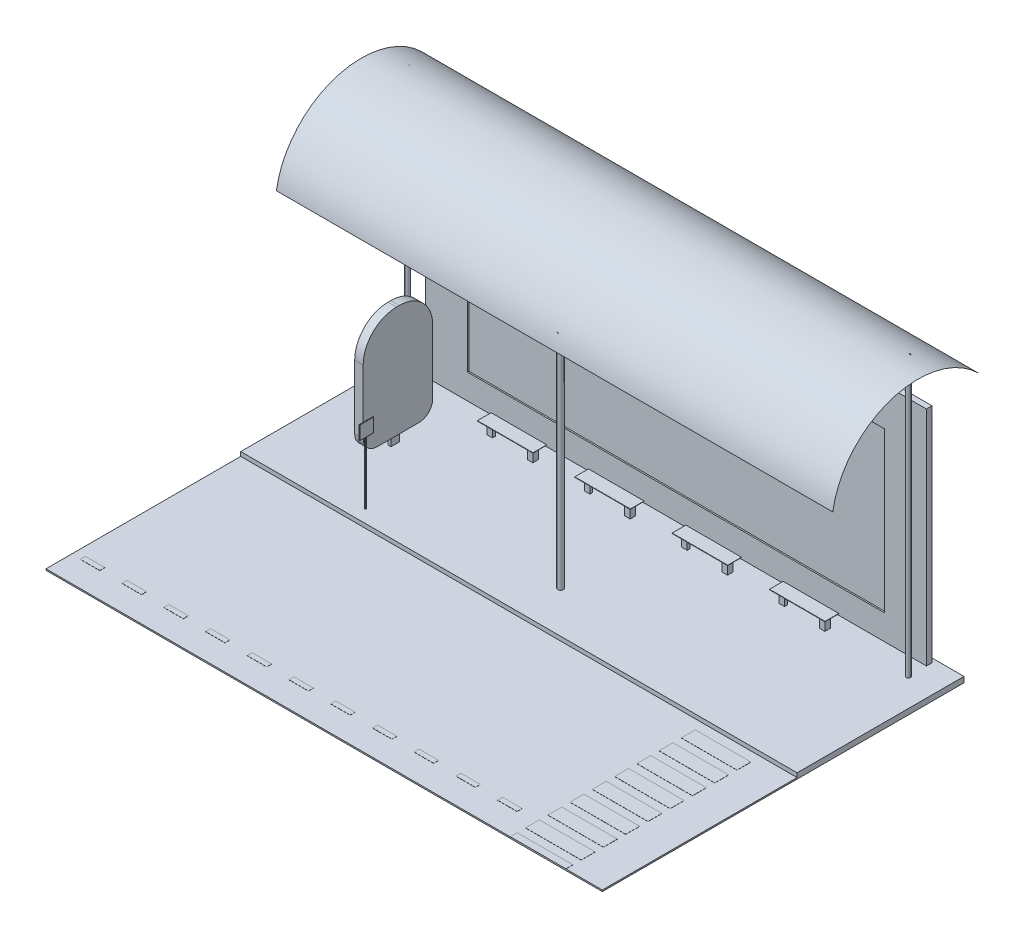
SolidWorks part; units mm, degrees
other "Camera1"
ref_plane "Front Plane" through (0, 0, 0) normal (0, 0, 1) x (1, 0, 0)
ref_plane "Top Plane" through (0, 0, 0) normal (0, 1, 0) x (1, 0, 0)
ref_plane "Right Plane" through (0, 0, 0) normal (1, 0, 0) x (0, 0, -1)
sketch "Sketch1" plane through (0, 0, 0) normal (0, 1, 0) x (1, 0, 0)
  line L1 (-2500, -6500) -> (17500, -6500)
  line L2 (-2500, -6500) -> (-2500, 6500)
  line L3 (-2500, 6500) -> (17500, 6500)
  line L4 (17500, -6500) -> (17500, 6500)
  point P0 (0, 0)
  dimension "D1" = 20000
  dimension "D2" = 13000
extrude "Boss-Extrude1" add sketch "Sketch1" along normal blind 200
sketch "Sketch2" plane through (0, 200, 0) normal (0, 1, 0) x (1, 0, 0)
  line L0 (-2500, 6500) -> (-2500, -6500) construction
  line L1 (17500, -6500) -> (-2500, -6500)
  line L2 (17500, -6500) -> (17500, 500)
  line L3 (17500, 500) -> (-2500, 500)
  line L4 (-2500, -6500) -> (-2500, 500)
  dimension "D1" = 7000
extrude "Calle" cut sketch "Sketch2" against normal blind 150 contours L3 L4 L1 L2
sketch "Sketch5" plane through (0, 50, 0) normal (0, 1, 0) x (1, 0, 0)
  line L0 (17500, -6500) -> (17500, -5500) construction
  line L1 (17500, -6500) -> (17500, 500) construction
  line L3 (17500, -5500) -> (-2500, -5500) construction
  line L4 (-2500, -6500) -> (-2500, 500) construction
  line L9 (24.9879, -5409.4917) -> (-675.0121, -5409.4917)
  line L10 (24.9879, -5590.5083) -> (-675.0121, -5590.5083)
  line L102 (15189.04, -6500) -> (15189.04, 500) construction
  line L107 (16189.04, -5450) -> (14189.04, -5450)
  line L108 (16189.04, -5950) -> (14189.04, -5950)
  line L109 (17500, -6500) -> (-2500, -6500) construction
  line L110 (17500, 500) -> (-2500, 500) construction
  line L111 (16189.04, -6250) -> (15189.04, -6500) construction
  line L112 (15189.04, -6500) -> (14189.04, -6250) construction
  line L113 (16189.04, -6250) -> (14189.04, -6250)
  line L117 (16189.04, -5450) -> (16189.04, -5950)
  line L118 (14189.04, -5450) -> (14189.04, -5950)
  line L119 (16189.04, -5450) -> (14189.04, -5950) construction
  line L120 (16189.04, -5950) -> (14189.04, -5450) construction
  line L121 (16189.04, -4650) -> (14189.04, -4650)
  line L122 (16189.04, -5150) -> (14189.04, -5150)
  line L123 (16189.04, -4650) -> (16189.04, -5150)
  line L124 (14189.04, -4650) -> (14189.04, -5150)
  line L125 (16189.04, -4650) -> (14189.04, -5150) construction
  line L126 (16189.04, -5150) -> (14189.04, -4650) construction
  line L127 (16189.04, -3850) -> (14189.04, -3850)
  line L128 (16189.04, -4350) -> (14189.04, -4350)
  line L129 (16189.04, -3850) -> (16189.04, -4350)
  line L130 (14189.04, -3850) -> (14189.04, -4350)
  line L131 (16189.04, -3850) -> (14189.04, -4350) construction
  line L132 (16189.04, -4350) -> (14189.04, -3850) construction
  line L133 (16189.04, -3050) -> (14189.04, -3050)
  line L134 (16189.04, -3550) -> (14189.04, -3550)
  line L135 (16189.04, -3050) -> (16189.04, -3550)
  line L136 (14189.04, -3050) -> (14189.04, -3550)
  line L137 (16189.04, -3050) -> (14189.04, -3550) construction
  line L138 (16189.04, -3550) -> (14189.04, -3050) construction
  line L139 (16189.04, -2250) -> (14189.04, -2250)
  line L140 (16189.04, -2750) -> (14189.04, -2750)
  line L141 (16189.04, -2250) -> (16189.04, -2750)
  line L142 (14189.04, -2250) -> (14189.04, -2750)
  line L143 (16189.04, -2250) -> (14189.04, -2750) construction
  line L144 (16189.04, -2750) -> (14189.04, -2250) construction
  line L145 (16189.04, -1450) -> (14189.04, -1450)
  line L146 (16189.04, -1950) -> (14189.04, -1950)
  line L147 (16189.04, -1450) -> (16189.04, -1950)
  line L148 (14189.04, -1450) -> (14189.04, -1950)
  line L149 (16189.04, -1450) -> (14189.04, -1950) construction
  line L150 (16189.04, -1950) -> (14189.04, -1450) construction
  line L151 (16189.04, -650) -> (14189.04, -650)
  line L152 (16189.04, -1150) -> (14189.04, -1150)
  line L153 (16189.04, -650) -> (16189.04, -1150)
  line L154 (14189.04, -650) -> (14189.04, -1150)
  line L155 (16189.04, -650) -> (14189.04, -1150) construction
  line L156 (16189.04, -1150) -> (14189.04, -650) construction
  line L157 (16189.04, 150) -> (14189.04, 150)
  line L158 (16189.04, -350) -> (14189.04, -350)
  line L159 (16189.04, 150) -> (16189.04, -350)
  line L160 (14189.04, 150) -> (14189.04, -350)
  line L161 (16189.04, 150) -> (14189.04, -350) construction
  line L162 (16189.04, -350) -> (14189.04, 150) construction
  line L163 (14189.04, -6250) -> (14189.04, -6500)
  line L164 (16189.04, -6250) -> (16189.04, -6500)
  line L165 (14189.04, -6500) -> (16189.04, -6500)
  line L174 (-1475.0121, -5590.5083) -> (-1475.0121, -5409.4917)
  line L175 (-1475.0121, -5409.4917) -> (-2175.0121, -5409.4917)
  line L176 (-1475.0121, -5590.5083) -> (-2175.0121, -5409.4917) construction
  line L177 (-1475.0121, -5590.5083) -> (-2175.0121, -5590.5083)
  line L178 (-2175.0121, -5590.5083) -> (-2175.0121, -5409.4917)
  line L179 (-1475.0121, -5409.4917) -> (-2175.0121, -5590.5083) construction
  line L181 (-675.0121, -5590.5083) -> (-675.0121, -5409.4917)
  line L182 (24.9879, -5590.5083) -> (24.9879, -5409.4917)
  line L183 (1524.9879, -5409.4917) -> (824.9879, -5409.4917)
  line L184 (1524.9879, -5590.5083) -> (824.9879, -5590.5083)
  line L185 (824.9879, -5590.5083) -> (824.9879, -5409.4917)
  line L186 (1524.9879, -5590.5083) -> (1524.9879, -5409.4917)
  line L187 (3024.9879, -5409.4917) -> (2324.9879, -5409.4917)
  line L188 (3024.9879, -5590.5083) -> (2324.9879, -5590.5083)
  line L189 (2324.9879, -5590.5083) -> (2324.9879, -5409.4917)
  line L190 (3024.9879, -5590.5083) -> (3024.9879, -5409.4917)
  line L191 (4524.9879, -5409.4917) -> (3824.9879, -5409.4917)
  line L192 (4524.9879, -5590.5083) -> (3824.9879, -5590.5083)
  line L193 (3824.9879, -5590.5083) -> (3824.9879, -5409.4917)
  line L194 (4524.9879, -5590.5083) -> (4524.9879, -5409.4917)
  line L195 (6024.9879, -5409.4917) -> (5324.9879, -5409.4917)
  line L196 (6024.9879, -5590.5083) -> (5324.9879, -5590.5083)
  line L197 (5324.9879, -5590.5083) -> (5324.9879, -5409.4917)
  line L198 (6024.9879, -5590.5083) -> (6024.9879, -5409.4917)
  line L199 (7524.9879, -5409.4917) -> (6824.9879, -5409.4917)
  line L200 (7524.9879, -5590.5083) -> (6824.9879, -5590.5083)
  line L201 (6824.9879, -5590.5083) -> (6824.9879, -5409.4917)
  line L202 (7524.9879, -5590.5083) -> (7524.9879, -5409.4917)
  line L203 (9024.9879, -5409.4917) -> (8324.9879, -5409.4917)
  line L204 (9024.9879, -5590.5083) -> (8324.9879, -5590.5083)
  line L205 (8324.9879, -5590.5083) -> (8324.9879, -5409.4917)
  line L206 (9024.9879, -5590.5083) -> (9024.9879, -5409.4917)
  line L207 (10524.9879, -5409.4917) -> (9824.9879, -5409.4917)
  line L208 (10524.9879, -5590.5083) -> (9824.9879, -5590.5083)
  line L209 (9824.9879, -5590.5083) -> (9824.9879, -5409.4917)
  line L210 (10524.9879, -5590.5083) -> (10524.9879, -5409.4917)
  line L211 (12024.9879, -5409.4917) -> (11324.9879, -5409.4917)
  line L212 (12024.9879, -5590.5083) -> (11324.9879, -5590.5083)
  line L213 (11324.9879, -5590.5083) -> (11324.9879, -5409.4917)
  line L214 (12024.9879, -5590.5083) -> (12024.9879, -5409.4917)
  line L215 (13524.9879, -5409.4917) -> (12824.9879, -5409.4917)
  line L216 (13524.9879, -5590.5083) -> (12824.9879, -5590.5083)
  line L217 (12824.9879, -5590.5083) -> (12824.9879, -5409.4917)
  line L218 (13524.9879, -5590.5083) -> (13524.9879, -5409.4917)
  point P13 (-1825.0121, -5500)
  dimension "D1" = 1000
  dimension "D3" = 9
extrude "Rayas de trafico" add sketch "Sketch5" along normal blind 5
sketch "Sketch6" plane through (0, 200, 0) normal (0, 1, 0) x (1, 0, 0)
  line L0 (-2500, 500) -> (-2500, 967.6651) construction
  line L1 (-2500, 6500) -> (-2500, 500) construction
  line L2 (1500, 967.6651) -> (-2500, 967.6651) construction
  line L3 (1540, 947.6651) -> (1500, 987.6651) construction
  line L10 (1540, 987.6651) -> (1500, 947.6651) construction
  line L11 (1500, 987.6651) -> (1500, 947.6651)
  line L12 (1540, 947.6651) -> (1500, 947.6651)
  line L13 (1540, 987.6651) -> (1540, 947.6651)
  line L14 (1540, 987.6651) -> (1500, 987.6651)
  dimension "D1" = 4000
extrude "Poste de la señal" add sketch "Sketch6" along normal blind 2500
sketch "Sketch8" plane through (1540, 0, 0) normal (1, 0, 0) x (0, 0, -1)
  line L0 (947.6651, 2700) -> (987.6651, 2700) construction
  line L1 (717.6651, 2950) -> (1217.6651, 2950)
  line L2 (717.6651, 2950) -> (717.6651, 2450)
  line L3 (717.6651, 2450) -> (1217.6651, 2450)
  line L4 (1217.6651, 2950) -> (1217.6651, 2450)
  line L5 (717.6651, 2950) -> (1217.6651, 2450) construction
  line L6 (717.6651, 2450) -> (1217.6651, 2950) construction
  point P0 (967.6651, 2700)
  dimension "D1" = 500
  dimension "D2" = 500
extrude "Señal de alto" add sketch "Sketch8" along normal blind 20
fillet "Fillet2" radius 10 4 edges at (1560, 2700, -717.6651) (1560, 2450, -967.6651) (1560, 2700, -1217.6651) (1560, 2950, -967.6651)
sketch "Sketch9" plane through (0, 200, 0) normal (0, 1, 0) x (1, 0, 0)
  line L0 (-2500, 6500) -> (-2500, 5500) construction
  line L1 (-2500, 6500) -> (-2500, 500) construction
  line L2 (-2500, 5500) -> (17500, 5500) construction
  line L3 (17500, 500) -> (17500, 6500) construction
  line L4 (-2500, 6500) -> (-1500, 6500) construction
  line L5 (17500, 6500) -> (-2500, 6500) construction
  line L6 (7500, 6500) -> (7500, 500) construction
  line L7 (17500, 500) -> (-2500, 500) construction
  circle A0 centre (-1500, 5500) radius 75
  circle A1 centre (16500, 5500) radius 75
  dimension "D3" = 150
  dimension "D1" = 1000
  dimension "D2" = 1000
extrude "Pilares externos" add sketch "Sketch9" along normal blind 10000
sketch "Sketch10" plane through (0, 200, 0) normal (0, 1, 0) x (1, 0, 0)
  line L0 (7500, 500) -> (7500, 2000) construction
  line L1 (17500, 500) -> (-2500, 500) construction
  circle A0 centre (7500, 2000) radius 100
  dimension "D2" = 200
  dimension "D1" = 1500
extrude "Pilar central" add sketch "Sketch10" along normal blind 8000
ref_plane "Plane1" through (17510, 0, 0) normal (1, 0, 0) x (0, 0, -1)
sketch "Sketch12" plane through (17510, 0, 0) normal (1, 0, 0) x (0, 0, -1)
  arc A0 (6993.3828, 9407.9851) -> (1772.1809, 7688.9264) centre (4828.0109, 7196.1862) ccw
  point P3 (5575, 10200)
  point P6 (5575, 10200)
  point P7 (6847.2328, 9510.8992)
  point P9 (1900, 8200)
  point P10 (1609.6207, 7734.0901)
surface "Techito" sketch "Sketch12" parameters "D1"=20000
sketch "Sketch13" plane through (0, 200, 0) normal (0, 1, 0) x (1, 0, 0)
  line L0 (-1500, 5500) -> (1500, 5500) construction
  line L1 (1500, 5500) -> (3000, 5500) construction
  line L2 (1500, 5500) -> (1500, 4900) construction
  line L3 (3000, 5500) -> (3000, 4900) construction
  circle A0 centre (1500, 5500) radius 35
  circle A1 centre (1500, 4900) radius 35
  circle A2 centre (3000, 5500) radius 35
  circle A3 centre (3000, 4900) radius 35
  dimension "D2" = 70
  dimension "D3" = 1500
  dimension "D1" = 3000
  dimension "D4" = 600
ref_plane "Plane2" [suppressed] through (3000, 0, 0) normal (1, 0, 0) x (0, 0, -1)
sketch "Sketch15" [suppressed] plane through (3000, 0, 0) normal (1, 0, 0) x (0, 0, -1)
  line L0 (5500, 200) -> (4900, 200) construction
  arc A0 (4900, 200) -> (5500, 200) centre (5200, 200) cw
  point P3 (5200, 200)
sweep "Sweep3" [suppressed] add profiles "Sketch13" path "Sketch15"
sketch "Sketch22" plane through (0, 200, 0) normal (0, 1, 0) x (1, 0, 0)
  line L0 (-1500, 5500) -> (1500, 5500) construction
  line L1 (1500, 5500) -> (3000, 5500) construction
  line L2 (1600, 5550) -> (1400, 5550)
  line L3 (1600, 5550) -> (1600, 5450)
  line L4 (1600, 5450) -> (1400, 5450)
  line L5 (1400, 5550) -> (1400, 5450)
  line L6 (1600, 5550) -> (1400, 5450) construction
  line L7 (1600, 5450) -> (1400, 5550) construction
  line L8 (5100, 5550) -> (4900, 5550)
  line L9 (2900, 5600) -> (3100, 5600)
  line L10 (2900, 5600) -> (2900, 5400)
  line L11 (2900, 5400) -> (3100, 5400)
  line L12 (3100, 5600) -> (3100, 5400)
  line L13 (2900, 5600) -> (3100, 5400) construction
  line L14 (2900, 5400) -> (3100, 5600) construction
  line L15 (5100, 5450) -> (4900, 5450)
  line L16 (4900, 5550) -> (4900, 5450)
  line L17 (5100, 5550) -> (5100, 5450)
  line L18 (6400, 5600) -> (6600, 5600)
  line L19 (6400, 5600) -> (6400, 5400)
  line L20 (6400, 5400) -> (6600, 5400)
  line L21 (6600, 5600) -> (6600, 5400)
  line L22 (8600, 5550) -> (8400, 5550)
  line L23 (8600, 5450) -> (8400, 5450)
  line L24 (8400, 5550) -> (8400, 5450)
  line L25 (8600, 5550) -> (8600, 5450)
  line L26 (9900, 5600) -> (10100, 5600)
  line L27 (9900, 5600) -> (9900, 5400)
  line L28 (9900, 5400) -> (10100, 5400)
  line L29 (10100, 5600) -> (10100, 5400)
  line L30 (12100, 5550) -> (11900, 5550)
  line L31 (12100, 5450) -> (11900, 5450)
  line L32 (11900, 5550) -> (11900, 5450)
  line L33 (12100, 5550) -> (12100, 5450)
  line L34 (13400, 5600) -> (13600, 5600)
  line L35 (13400, 5600) -> (13400, 5400)
  line L36 (13400, 5400) -> (13600, 5400)
  line L37 (13600, 5600) -> (13600, 5400)
  dimension "D1" = 3000
  dimension "D2" = 100
  dimension "D3" = 200
  dimension "D4" = 1500
  dimension "D5" = 200
  dimension "D6" = 200
  dimension "D7" = 4
extrude "Patas de las bancas" add sketch "Sketch22" along normal blind 450
sketch "Sketch23" plane through (0, 650, 0) normal (0, 1, 0) x (1, 0, 0)
  line L0 (3100, 5500) -> (1400, 5500) construction
  line L1 (3100, 5400) -> (3100, 5600) construction
  line L2 (1400, 5550) -> (1400, 5450) construction
  line L3 (6750, 5750) -> (4750, 5750)
  line L4 (3250, 5750) -> (1250, 5750)
  line L5 (3250, 5750) -> (3250, 5250)
  line L6 (3250, 5250) -> (1250, 5250)
  line L7 (1250, 5750) -> (1250, 5250)
  line L8 (3250, 5750) -> (1250, 5250) construction
  line L9 (3250, 5250) -> (1250, 5750) construction
  line L10 (6750, 5750) -> (6750, 5250)
  line L11 (4750, 5750) -> (4750, 5250)
  line L12 (6750, 5250) -> (4750, 5250)
  line L13 (10250, 5750) -> (8250, 5750)
  line L14 (10250, 5750) -> (10250, 5250)
  line L15 (8250, 5750) -> (8250, 5250)
  line L16 (10250, 5250) -> (8250, 5250)
  line L17 (13750, 5750) -> (11750, 5750)
  line L18 (13750, 5750) -> (13750, 5250)
  line L19 (11750, 5750) -> (11750, 5250)
  line L20 (13750, 5250) -> (11750, 5250)
  point P6 (2250, 5500)
  dimension "D1" = 2000
  dimension "D2" = 500
  dimension "D3" = 4
extrude "Asiento de las bancas" add sketch "Sketch23" along normal blind 10
fillet "Fillet3" radius 10 4 edges at (12750, 660, -5250) (9250, 660, -5250) (5750, 660, -5250) (2250, 660, -5250)
sketch "Sketch24" plane through (0, 200, 0) normal (0, 1, 0) x (1, 0, 0)
  line L0 (6750, 5750) -> (8250, 5750) construction
  line L2 (6750, 5750) -> (4750, 5750) construction
  line L3 (10250, 5750) -> (8250, 5750) construction
  line L4 (7500, 5750) -> (7500, 6250) construction
  line L6 (16500, 6350) -> (-1500, 6350)
  line L7 (16500, 6350) -> (16500, 6150)
  line L8 (16500, 6150) -> (-1500, 6150)
  line L9 (-1500, 6350) -> (-1500, 6150)
  line L10 (16500, 6350) -> (-1500, 6150) construction
  line L11 (16500, 6150) -> (-1500, 6350) construction
  dimension "D1" = 500
  dimension "D2" = 200
  dimension "D3" = 18000
extrude "Muro de separación" add sketch "Sketch24" along normal blind 8000
sketch "Sketch26" plane through (0, 0, -6350) normal (0, 0, -1) x (-1, 0, 0)
  line L0 (1500, 200) -> (0, 200) construction
  line L1 (-16500, 200) -> (1500, 200) construction
  line L2 (1500, 200) -> (1500, 1100) construction
  line L3 (1500, 8200) -> (1500, 200) construction
  line L4 (-15000, 1100) -> (-16500, 1100) construction
  line L5 (0, 1100) -> (-15000, 1100)
  line L6 (0, 1100) -> (0, 6827.9987)
  line L7 (0, 6827.9987) -> (-15000, 6827.9987)
  line L8 (-15000, 1100) -> (-15000, 6827.9987)
  line L9 (-16500, 8200) -> (-16500, 200) construction
  point P12 (-961.8831, 1100)
  point P16 (0, 1100)
  point P17 (0, 0)
  dimension "D1" = 1500
  dimension "D2" = 900
  dimension "D3" = 1500
extrude "Hueco ventana" cut sketch "Sketch26" against normal up to next
sketch "Sketch27" plane through (0, 1100, 0) normal (0, 1, 0) x (1, 0, 0)
  line L0 (0, 6250) -> (15000, 6250) construction
  line L1 (0, 6150) -> (0, 6350) construction
  line L2 (15000, 6150) -> (15000, 6350) construction
  line L4 (0, 6200) -> (15000, 6200)
  line L5 (0, 6200) -> (0, 6300)
  line L6 (0, 6300) -> (15000, 6300)
  line L7 (15000, 6200) -> (15000, 6300)
  line L8 (0, 6200) -> (15000, 6300) construction
  line L9 (0, 6300) -> (15000, 6200) construction
  point P6 (7500, 6250)
  dimension "D1" = 100
extrude "Ventana" add sketch "Sketch27" along normal up to next
sketch "Sketch28" plane through (0, 200, 0) normal (0, 1, 0) x (1, 0, 0)
  line L0 (-2500, 3500) -> (0, 3500) construction
  line L1 (-2500, 6500) -> (-2500, 500) construction
  line L2 (0, 3500) -> (0, 6500) construction
  line L16 (50, 3650) -> (-50, 3650)
  line L17 (50, 3650) -> (50, 3350)
  line L18 (50, 3350) -> (-50, 3350)
  line L19 (-50, 3650) -> (-50, 3350)
  line L20 (50, 3650) -> (-50, 3350) construction
  line L21 (50, 3350) -> (-50, 3650) construction
  dimension "D1" = 2500
  dimension "D2" = 100
  dimension "D3" = 300
extrude "Boss-Extrude13" add sketch "Sketch28" along normal blind 350
sketch "Sketch29" plane through (0, 550, 0) normal (0, 1, 0) x (1, 0, 0)
  line L0 (50, 3500) -> (-50, 3500) construction
  line L1 (50, 3350) -> (50, 3650) construction
  line L2 (-50, 3650) -> (-50, 3350) construction
  line L3 (0, 3650) -> (0, 3350) construction
  line L4 (50, 3650) -> (-50, 3650) construction
  line L5 (-50, 3350) -> (50, 3350) construction
  line L7 (152.5442, 4750) -> (-152.5442, 4750)
  line L8 (152.5442, 4750) -> (152.5442, 2250)
  line L9 (152.5442, 2250) -> (-152.5442, 2250)
  line L10 (-152.5442, 4750) -> (-152.5442, 2250)
  line L11 (152.5442, 4750) -> (-152.5442, 2250) construction
  line L12 (152.5442, 2250) -> (-152.5442, 4750) construction
  point P12 (0, 3500)
  dimension "D1" = 2500
extrude "Boss-Extrude14" add sketch "Sketch29" along normal blind 4000
fillet "Fillet4" radius 1200 2 edges at (0, 4550, -4750) (0, 4550, -2250)
fillet "Fillet5" radius 500 2 edges at (0, 550, -4750) (0, 550, -2250)
